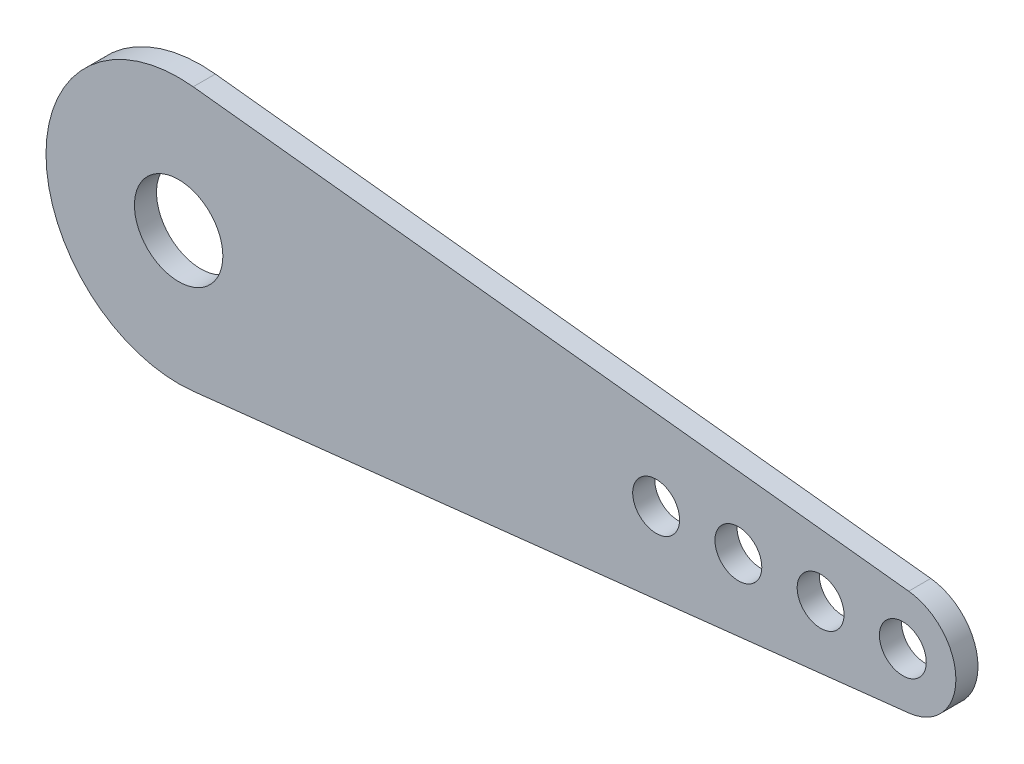
SolidWorks part; units mm, degrees
material "AISI 4340 Steel, normalized"
ref_plane "X-Y Datum" through (0, 0, 0) normal (0, 0, 1) x (1, 0, 0)
ref_plane "X-Z Datum" through (0, 0, 0) normal (0, 1, 0) x (1, 0, 0)
ref_plane "Y-Z Datum" through (0, 0, 0) normal (1, 0, 0) x (0, 0, -1)
sketch "Flat sketch" plane through (0, 0, 0) normal (0, 0, 1) x (1, 0, 0)
  line L0 (-6.35, 0) -> (104.013, 0) construction
  line L2 (2.0934, 18.9346) -> (104.8504, 7.5739)
  line L3 (2.0934, -18.9346) -> (104.8504, -7.5739)
  line L4 (104.8504, 7.5739) -> (104.8504, -7.5739) construction
  circle A0 centre (0, 0) radius 6.35
  circle A1 centre (0, 0) radius 19.05
  circle A2 centre (104.013, 0) radius 3.3655
  circle A8 centre (104.013, 0) radius 7.62
  circle A9 centre (92.202, 0) radius 3.3655
  circle A10 centre (80.391, 0) radius 3.3655
  circle A11 centre (68.58, 0) radius 3.3655
  point P5 (6.35, 0)
  point P9 (19.05, 0)
  point P10 (-19.05, 0)
  point P16 (111.633, 0)
  dimension "D1" = 12.7
  dimension "D2" = 38.1
  dimension "D3" = 6.731
  dimension "D7" = 15.24
  dimension "D6" = 11.811
  dimension "D8" = 130.683
  dimension "D5" = 68.58
  dimension "D4" = 4
extrude "Extrude face" add sketch "Flat sketch" along normal blind 3.175 contours A1 A0 | A8 A2 | A11 | A10 | A9 | A2 | A8 L2 A1 L3 A11 A10 A9 region at (50.441, 0, 0) region at (13.7898, 12.3493, 0) region at (109.5289, 4.9397, 0) region at (104.013, 0, 0) region at (92.202, 0, 0) region at (80.391, 0, 0) region at (68.58, 0, 0)
extrude "Extrude cut - holes" cut sketch "Flat sketch<4>" along normal up to surface (3.175 mm away) contours A11 | A10 | A9 | A2 region at (104.013, 0, 0) region at (92.202, 0, 0) region at (80.391, 0, 0) region at (68.58, 0, 0) up to face at (6.35, 0, 3.175)
sketch "Flat sketch<4>" plane through (0, 0, 0) normal (0, 0, 1) x (1, 0, 0) same geometry as "Flat sketch"
equation "\"Torsion Bar O.D.\"= 0.5"
equation "\"Lever I.D. Torsion O.D. Clearance\"= 0"
equation "\"Lever I.D.\"= \"Torsion Bar O.D.\" + \"Lever I.D. Torsion O.D. Clearance\""
equation "\"D1@Flat sketch\" = \"Lever I.D.\""
equation "\"Lever O.D.\"= 1.5"
equation "\"D2@Flat sketch\" = \"Lever O.D.\""
equation "\"Lever Rod end I.D.\"= 0.265"
equation "\"D3@Flat sketch\" = \"Lever Rod end I.D.\""
equation "\"Distance b/w Lever Rod end holes\"= 0"
equation "\"Number of Lever Rod end holes\"= 0"
equation "\"Lever arc radius\"= 0.5"
equation "\"First Lever droplink hole length\"= 2.7"
equation "\"Lever thickness\"= 1 / 8in"
equation "\"D1@Extrude face\" = \"Lever thickness\""
equation "\"D5@Flat sketch\"=\"First Lever droplink hole length\""
